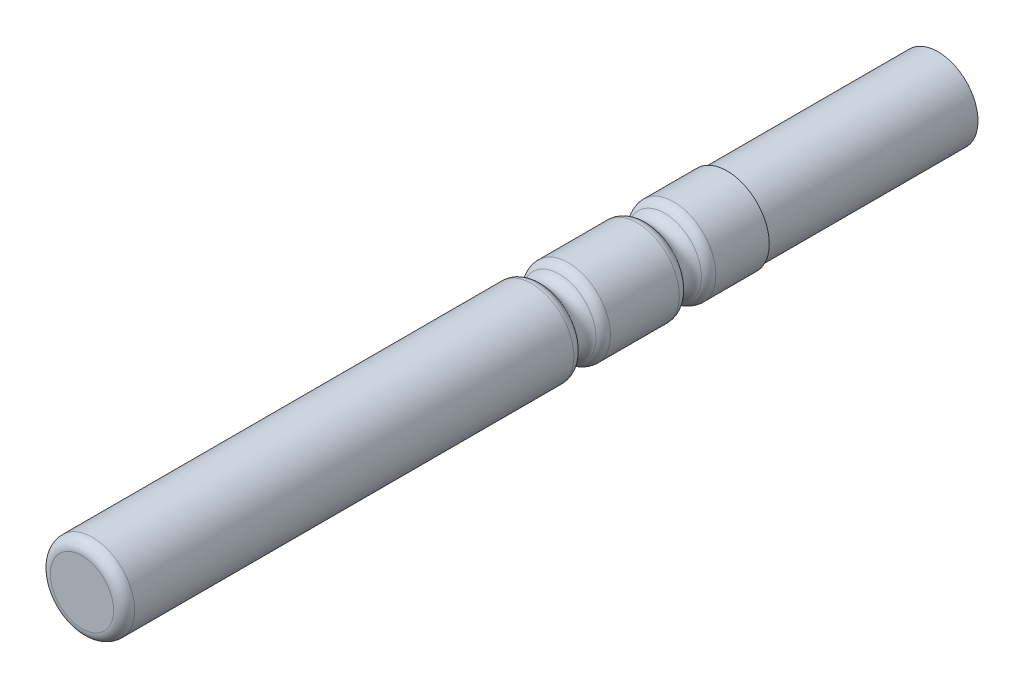
SolidWorks part; units mm, degrees
ref_plane "Front Plane" through (0, 0, 0) normal (0, 0, 1) x (1, 0, 0)
ref_plane "Top Plane" through (0, 0, 0) normal (0, 1, 0) x (1, 0, 0)
ref_plane "Right Plane" through (0, 0, 0) normal (1, 0, 0) x (0, 0, -1)
sketch "Sketch1" plane through (0, 0, 0) normal (0, 0, 1) x (1, 0, 0)
  circle A0 centre (0, 0) radius 2
  dimension "D1" = 4
extrude "Boss-Extrude1" add sketch "Sketch1" along normal blind 30.6
sketch "Sketch2" plane through (0, 0, 0) normal (1, 0, 0) x (0, 0, -1)
  line L0 (0, 2) -> (-30.6, 2) construction
  line L1 (0, 0) -> (-8.9676, 0) construction
  circle A0 centre (-3.4, 2) radius 0.5
  circle A1 centre (-8.4, 2) radius 0.5
  dimension "D1" = 1
  dimension "D2" = 3.4
  dimension "D3" = 8.4
revolve "Cut-Revolve1" cut sketch "Sketch2" angle 360 about L1
fillet "Fillet1" radius 0.5 5 edges at (0, 2, 3.9) (0, -2, 2.9) (0, 2, 8.9) (0, -2, 7.9) (2, 0, 30.6)
sketch "Sketch3" plane through (0, 0, 0) normal (0, 0, 1) x (1, 0, 0)
  circle A0 centre (0, 0) radius 1.9
  dimension "D1" = 3.8
extrude "Boss-Extrude2" add sketch "Sketch3" against normal blind 10
